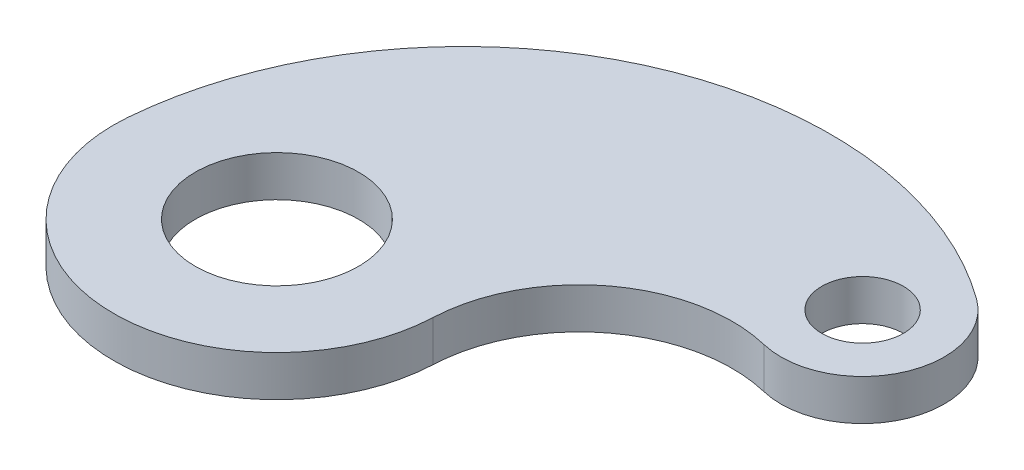
SolidWorks part; units mm, degrees
ref_plane "Alzado" through (0, 0, 0) normal (0, 0, 1) x (1, 0, 0)
ref_plane "Planta" through (0, 0, 0) normal (0, 1, 0) x (1, 0, 0)
ref_plane "Vista lateral" through (0, 0, 0) normal (1, 0, 0) x (0, 0, -1)
sketch "Croquis2" plane through (0, 0, 0) normal (0, 1, 0) x (1, 0, 0)
  line L0 (0, 0) -> (0, -15.2206) construction
  line L1 (0, 0) -> (181.8653, 105) construction
  circle A0 centre (0, 0) radius 40
  circle A1 centre (181.8653, 105) radius 20
  arc A2 (172.4692, 66.1192) -> (205.3545, 137.3769) centre (181.8653, 105) ccw
  arc A3 (-79.7227, 6.6552) -> (79.9234, -3.5005) centre (0, 0) ccw
  arc A4 (79.9234, -3.5005) -> (172.4692, 66.1192) centre (154.8515, -6.7822) cw
  arc A5 (-79.7227, 6.6552) -> (205.3545, 137.3769) centre (99.6534, -8.319) cw
  dimension "D1" = 80
  dimension "D2" = 40
  dimension "D5" = 80
  dimension "D6" = 160
  dimension "D7" = 75
  dimension "D8" = 180
  dimension "D3" = 210
  dimension "D4" = 120
extrude "Saliente-Extruir1" add sketch "Croquis2" along normal blind 10 and the other way blind 10
